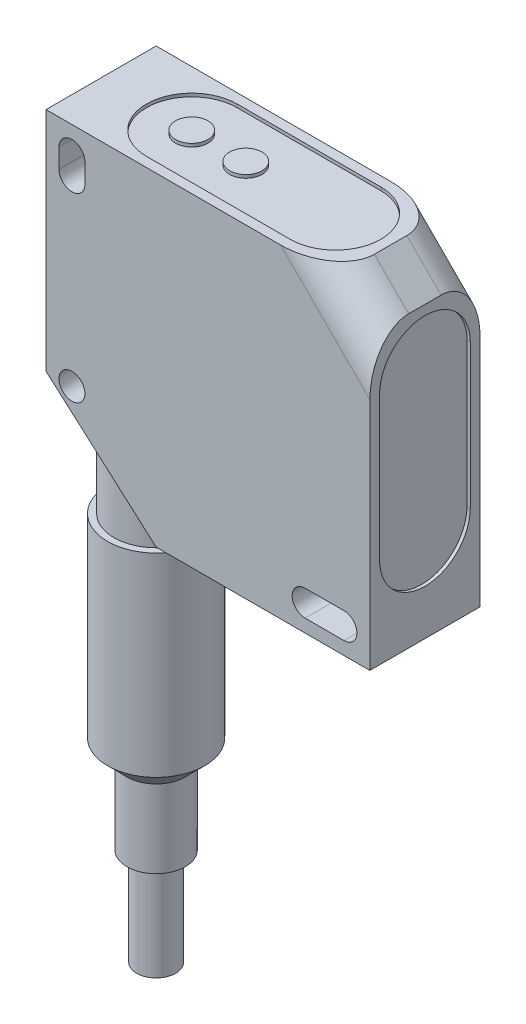
SolidWorks part; units mm, degrees
ref_plane "Plan de face" through (0, 0, 0) normal (0, 0, 1) x (1, 0, 0)
ref_plane "Plan de dessus" through (0, 0, 0) normal (0, 1, 0) x (1, 0, 0)
ref_plane "Plan de droite" through (0, 0, 0) normal (1, 0, 0) x (0, 0, -1)
sketch "Esquisse1" plane through (0, 0, 0) normal (0, 0, 1) x (1, 0, 0)
  line L0 (0, 50) -> (0, 15)
  line L1 (0, 15) -> (17, 0)
  line L2 (17, 0) -> (50, 0)
  line L3 (50, 0) -> (50, 44.6967)
  line L4 (50, 44.6967) -> (44.6967, 50)
  line L5 (44.6967, 50) -> (0, 50)
  line L6 (2, 43) -> (2, 46)
  line L7 (6, 46) -> (6, 43)
  line L8 (4, 48) -> (4, 15) construction
  line L9 (0, 15) -> (4, 15) construction
  line L10 (50, 4) -> (17.3738, 4) construction
  line L11 (40, 6) -> (46, 6)
  line L12 (46, 2) -> (40, 2)
  arc A0 (2, 46) -> (6, 46) centre (4, 46) cw
  arc A1 (2, 43) -> (6, 43) centre (4, 43) ccw
  circle A2 centre (4, 15) radius 2
  arc A3 (46, 6) -> (46, 2) centre (46, 4) cw
  arc A4 (40, 6) -> (40, 2) centre (40, 4) ccw
  dimension "D11" = 4
  dimension "D1" = 50
  dimension "D2" = 50
  dimension "D3" = 33
  dimension "D4" = 35
  dimension "D5" = 45
  dimension "D6" = 7.5
  dimension "D7" = 4
  dimension "D8" = 3
  dimension "D9" = 2
  dimension "D10" = 4
  dimension "D12" = 4
  dimension "D13" = 4
  dimension "D14" = 6
  dimension "D15" = 4
extrude "Extrusion1" add sketch "Esquisse1" along normal blind 17
fillet "Congé1" radius 6 2 edges at (47.3483, 47.3483, 0) (47.3483, 47.3483, 17)
sketch "Esquisse5" plane through (0, 0, 0) normal (0, -1, 0) x (1, 0, 0)
  line L0 (17, 8.5) -> (0, 8.5) construction
  line L1 (17, 17) -> (17, 0) construction
  line L2 (0, 17) -> (0, 0) construction
  line L3 (8.5, 17) -> (8.5, 0) construction
  line L4 (0, 17) -> (17, 17) construction
  line L5 (0, 0) -> (17, 0) construction
  circle A0 centre (8.5, 8.5) radius 6.5
  dimension "D1" = 13
extrude "Extrusion3" add sketch "Esquisse5" along normal blind 4 and the other way up to next
sketch "Esquisse6" plane through (0, -4, 0) normal (0, -1, 0) x (1, 0, 0)
  circle A0 centre (8.5, 8.5) radius 7.5
  dimension "D1" = 15
extrude "Extrusion4" add sketch "Esquisse6" along normal blind 30
sketch "Esquisse7" plane through (0, -34, 0) normal (0, -1, 0) x (1, 0, 0)
  circle A0 centre (8.5, 8.5) radius 4.5
  dimension "D1" = 9
extrude "Extrusion5" add sketch "Esquisse7" along normal blind 15
chamfer "Chanfrein2" distance 3 angle 45 1 edges at (8.5, -34, 4)
sketch "Esquisse8" plane through (0, -49, 0) normal (0, -1, 0) x (1, 0, 0)
  circle A0 centre (8.5, 8.5) radius 3
  dimension "D1" = 6
extrude "Extrusion6" add sketch "Esquisse8" along normal blind 15
chamfer "Chanfrein3" distance 1 angle 45 1 edges at (8.5, -49, 5.5)
sketch "Esquisse9" plane through (50, 0, 0) normal (1, 0, 0) x (0, 0, -1)
  line L0 (-8.5, 44.6967) -> (-8.5, 0) construction
  line L1 (-11, 44.6967) -> (-6, 44.6967) construction
  line L2 (-17, 0) -> (0, 0) construction
  line L3 (-15.5, 14) -> (-15.5, 36.1967)
  line L4 (-1.5, 36.1967) -> (-1.5, 14)
  line L5 (-17, 0) -> (-17, 36.2114) construction
  arc A0 (-15.5, 36.1967) -> (-1.5, 36.1967) centre (-8.5, 36.1967) cw
  arc A1 (-15.5, 14) -> (-1.5, 14) centre (-8.5, 14) ccw
  point P12 (-8.5, 7)
  point P15 (-8.5, 43.1967)
  dimension "D1" = 1.5
  dimension "D2" = 7
  dimension "D3" = 1.5
extrude "Extrusion7" cut sketch "Esquisse9" against normal blind 0.5
sketch "Esquisse10" plane through (0, 50, 0) normal (0, 1, 0) x (1, 0, 0)
  line L0 (0, -8.5) -> (44.6967, -8.5) construction
  line L1 (0, -17) -> (0, 0) construction
  line L2 (44.6967, -11) -> (44.6967, -6) construction
  line L3 (14, -1.5) -> (36.1967, -1.5)
  line L4 (36.1967, -15.5) -> (14, -15.5)
  line L5 (36.2114, 0) -> (0, 0) construction
  arc A0 (36.1967, -1.5) -> (36.1967, -15.5) centre (36.1967, -8.5) cw
  arc A1 (14, -1.5) -> (14, -15.5) centre (14, -8.5) ccw
  circle A2 centre (14, -8.5) radius 2.5
  circle A3 centre (22.3483, -8.5) radius 2.5
  point P12 (7, -8.5)
  point P13 (43.1967, -8.5)
  dimension "D4" = 5
  dimension "D1" = 7
  dimension "D2" = 1.5
  dimension "D3" = 1.5
extrude "Extrusion8" cut sketch "Esquisse10" against normal blind 0.5
